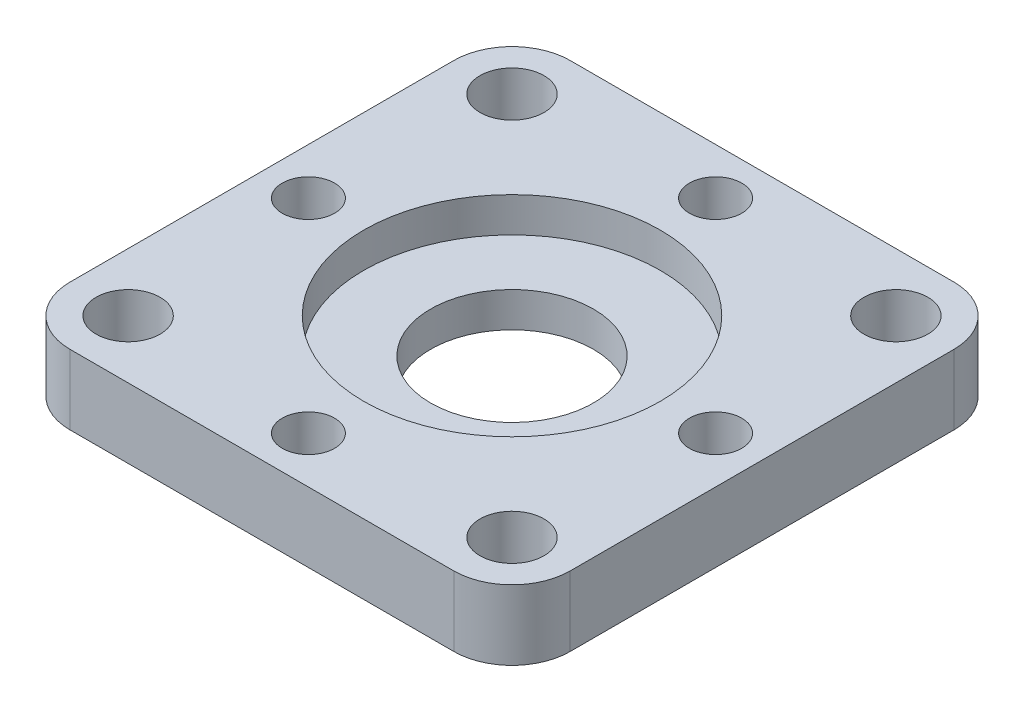
SolidWorks part; units mm, degrees
ref_plane "Front Plane" through (0, 0, 0) normal (0, 0, 1) x (1, 0, 0)
ref_plane "Top Plane" through (0, 0, 0) normal (0, 1, 0) x (1, 0, 0)
ref_plane "Right Plane" through (0, 0, 0) normal (1, 0, 0) x (0, 0, -1)
sketch "Sketch1" plane through (0, 0, 0) normal (0, 1, 0) x (1, 0, 0)
  line L1 (-16.5, -16.5) -> (16.5, -16.5)
  line L2 (-16.5, -16.5) -> (-16.5, 16.5)
  line L3 (-16.5, 16.5) -> (16.5, 16.5)
  line L4 (16.5, -16.5) -> (16.5, 16.5)
  line L5 (-16.5, -16.5) -> (16.5, 16.5) construction
  line L6 (-16.5, 16.5) -> (16.5, -16.5) construction
  line L7 (21.5, -21.5) -> (-21.5, -21.5)
  line L8 (21.5, -21.5) -> (21.5, 21.5)
  line L9 (21.5, 21.5) -> (-21.5, 21.5)
  line L10 (-21.5, -21.5) -> (-21.5, 21.5)
  line L11 (21.5, -21.5) -> (-21.5, 21.5) construction
  line L12 (21.5, 21.5) -> (-21.5, -21.5) construction
  circle A0 centre (-16.5, 16.5) radius 2.75
  circle A1 centre (16.5, 16.5) radius 2.75
  circle A2 centre (-16.5, -16.5) radius 2.75
  circle A3 centre (16.5, -16.5) radius 2.75
  point P0 (0, 0)
  point P10 (0, 0)
  dimension "D3" = 5
  dimension "D1" = 33
  dimension "D2" = 33
  dimension "D4" = 5
extrude "Boss-Extrude1" add sketch "Sketch1" along normal blind 6 contours L10 L7 L8 L9 A3 L1 A2 L2 A0 L3 A1 L4 | A3 L4 A1 L3 A0 L2 A2 L1 region at (0, 0, 0) region at (0, 0, 20.8919)
sketch "Sketch2" plane through (0, 6, 0) normal (0, 1, 0) x (1, 0, 0)
  circle A0 centre (0, 0) radius 7
extrude "Cut-Extrude1" cut sketch "Sketch2" against normal blind 6
sketch "Sketch3" plane through (0, 6, 0) normal (0, 1, 0) x (1, 0, 0)
  circle A0 centre (0, 0) radius 17.5
  circle A1 centre (0, 17.5) radius 2.25
  circle A2 centre (17.5, 0) radius 2.25
  circle A3 centre (0, -17.5) radius 2.25
  circle A4 centre (-17.5, 0) radius 2.25
extrude "Cut-Extrude2" cut sketch "Sketch3" against normal blind 6 contours A0 A1 | A0 A1 | A0 A2 | A0 A2 | A0 A4 | A0 A4 | A0 A3 | A0 A3 region at (16.5195, 6, 0) region at (18.4284, 6, 0) region at (0, 6, -16.5195) region at (0, 6, -18.4284) region at (0, 6, 18.4284) region at (0, 6, 16.5195) region at (-16.5195, 6, 0) region at (-18.4284, 6, 0)
sketch "Sketch4" plane through (0, 6, 0) normal (0, 1, 0) x (1, 0, 0)
  circle A0 centre (0, 0) radius 12.75
extrude "Cut-Extrude3" cut sketch "Sketch4" against normal blind 3
fillet "Fillet1" radius 5 4 edges at (-21.5, 3, 21.5) (21.5, 3, 21.5) (21.5, 3, -21.5) (-21.5, 3, -21.5)
